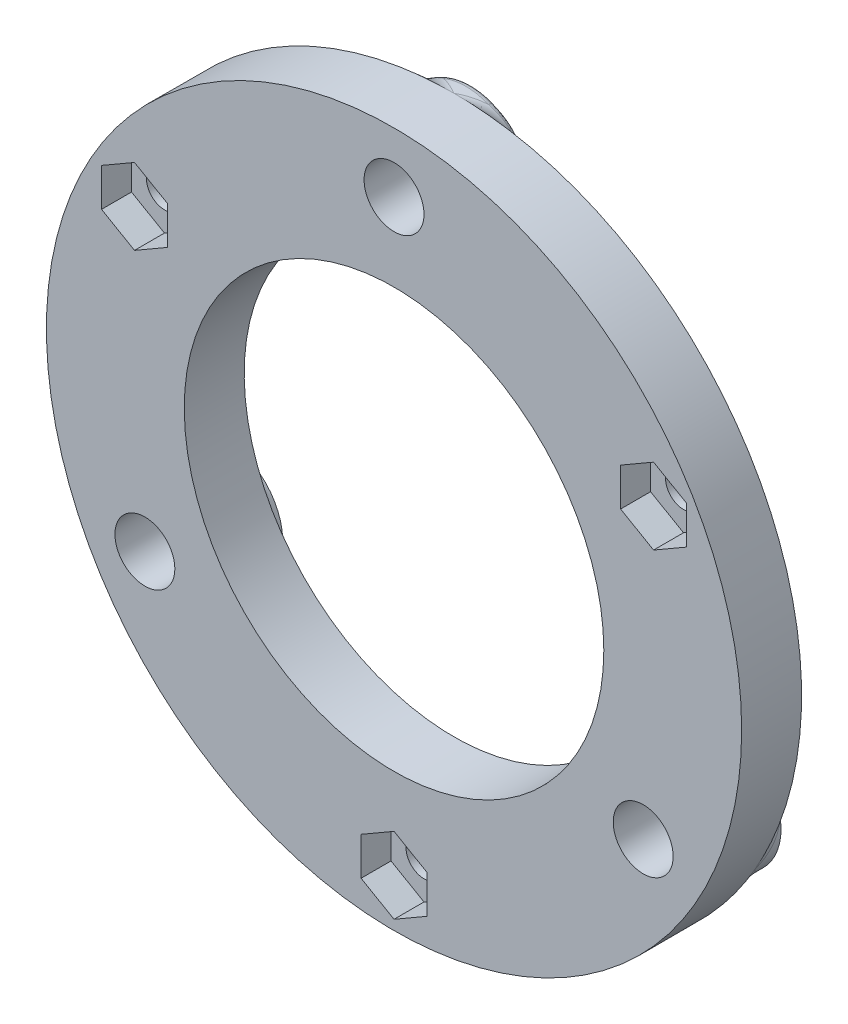
SolidWorks part; units mm, degrees
ref_plane "Front Plane" through (0, 0, 0) normal (0, 0, 1) x (1, 0, 0)
ref_plane "Top Plane" through (0, 0, 0) normal (0, 1, 0) x (1, 0, 0)
ref_plane "Right Plane" through (0, 0, 0) normal (1, 0, 0) x (0, 0, -1)
sketch "Sketch2" plane through (0, 0, 0) normal (0, 0, 1) x (1, 0, 0)
  line L0 (0, 24) -> (0, 0) construction
  line L1 (0, 0) -> (21.6506, 12.5) construction
  circle A0 centre (0, 0) radius 29
  circle A1 centre (0, 0) radius 17.5
  circle A2 centre (0, 0) radius 24 construction
  circle A3 centre (0, 24) radius 2.5
  circle A4 centre (0, 0) radius 25 construction
  circle A5 centre (20.7846, -12) radius 2.5
  circle A8 centre (21.6506, 12.5) radius 1.5
  circle A9 centre (0, -25) radius 1.5
  circle A11 centre (0, 0) radius 8 construction
  circle A14 centre (0, 24) radius 5 construction
  circle A15 centre (0, 0) radius 19 construction
  circle A16 centre (-20.7846, -12) radius 2.5
  circle A19 centre (-21.6506, 12.5) radius 1.5
  point P17 (0, 0)
  point P24 (0, 0)
  dimension "D1" = 58
  dimension "D2" = 48
  dimension "D4" = 5
  dimension "D7" = 3
  dimension "D3" = 16
  dimension "D10" = 10
  dimension "D5" = 4
  dimension "D9" = 1.5
  dimension "D11" = 60
  dimension "D6" = 3
  dimension "D8" = 3
extrude "Boss-Extrude1" add sketch "Sketch2" along normal blind 5
sketch "Sketch3" plane through (0, 0, 5) normal (0, 0, 1) x (1, 0, 0)
  line L0 (0, 24) -> (0, 0) construction
  line L13 (-0.5774, 24) -> (-0.2887, 23.5)
  line L14 (-0.2887, 23.5) -> (0.2887, 23.5)
  line L15 (0.2887, 23.5) -> (0.5774, 24)
  line L16 (0.5774, 24) -> (0.2887, 24.5)
  line L17 (0.2887, 24.5) -> (-0.2887, 24.5)
  line L18 (-0.2887, 24.5) -> (-0.5774, 24)
  line L20 (21.6506, 9.3246) -> (24.4006, 10.9123)
  line L21 (24.4006, 10.9123) -> (24.4006, 14.0877)
  line L22 (24.4006, 14.0877) -> (21.6506, 15.6754)
  line L23 (21.6506, 15.6754) -> (18.9006, 14.0877)
  line L24 (18.9006, 14.0877) -> (18.9006, 10.9123)
  line L25 (18.9006, 10.9123) -> (21.6506, 9.3246)
  circle A0 centre (0, 24) radius 0.5 construction
  circle A1 centre (21.6506, 12.5) radius 2.75 construction
  dimension "D1" = 1
  dimension "D2" = 5.5
extrude "Cut-Extrude1" cut sketch "Sketch3" against normal blind 2.5
pattern_circular "CirPattern1" count 3 over 360 about axis through (0, 0, 5) along (0, 0, -1) of "Cut-Extrude1" reverse direction yes
sketch "Sketch4" plane through (0, 0, 0) normal (0, 0, -1) x (-1, 0, 0)
  circle A0 centre (0, 24) radius 4
  circle A1 centre (0, 24) radius 5
  dimension "D1" = 8
extrude "Boss-Extrude2" add sketch "Sketch4" along normal blind 1.5
fillet "Fillet1" radius 1.5 1 edges at (-5, 24, 0)
fillet "Fillet2" radius 0.5 2 edges at (0, 29, -1.5) (0, 19, -1.5)
chamfer "Chamfer1" distance 0.25 angle 45 1 edges at (-4, 24, -1.5)
pattern_circular "CirPattern2" count 3 over 360 about axis through (0, 0, 5) along (0, 0, -1) of "Fillet1", "Boss-Extrude2", "Chamfer1" reverse direction yes
equation "\"Nr\"= \"Ns\" + 2 * \"Np\"'num teeth"
equation "\"module\"= 0.8"
equation "\"pressure_angle\"= 20deg"
equation "\"h_a\"= 1 * \"module\"'addendum"
equation "\"h_f\"= 1.25 * \"module\"'dedendum"
equation "\"clr_tip_root\"= \"h_f\" - \"h_a\"'clearance of gear tooth tip and root"
equation "\"dp_r\"= \"module\" * \"Nr\"'PCD"
equation "\"db_r\"= \"dp_r\" * cos ( \"pressure_angle\" )'base CD"
equation "\"fw_r\"= 11.5mm'face width"
equation "\"alpha_r\"= sqr ( \"dp_r\" ^ 2 - \"db_r\" ^ 2 ) / \"db_r\" * 180 / pi - \"pressure_angle\""
equation "\"beta_r\"= ( 360 / ( 4 * \"Nr\" ) + \"alpha_r\" ) * 2"
equation "\"bearing_ID\"= \"module\" * ( \"Ns\" + \"Np\" ) + 10"
equation "\"bearing_OD\"= 1.18 * \"bearing_ID\" + 8.57"
equation "\"bearing_height\"= 0.09 * \"bearing_ID\" + 4.62"
equation "\"clearance_planet\"=1.5"
equation "\"case_dist\"= \"sec_carrier_thickness\" + \"clearance_planet\" + \"standard_clearance_1_5mm\""
equation "\"Motor_case_OD_max\"= \"case_mounting_PCD\" + \"case_mounting_hole_allen_socket_dia\" + \"clearance_case_mount_holes_shell_thickness\" * 2"
equation "\"case_mounting_PCD\"= \"motor_case_OD_base\" + \"case_mounting_hole_shift\" * 2"
equation "\"bearing mount thickness\"= IIF((\"bearing_OD\" + \"output_mounting_hole_dia\" * 4) > (\"Nr\" * \"module\" + 2 * \"h_b\"), \"output_mounting_hole_dia\" * 2, ((\"Nr\" * \"module\" + 2 * \"h_b\" - (\"bearing_OD\" + \"output_mounting_hole_dia\" * 4)) / 2) + \"output_mounting_hole_dia\" * 2 + \"standard_clearance_1_5mm\")"
equation "\"case_mounting_hole_dia\"=3"
equation "\"output_mounting_PCD\"= \"bearing_OD\" + \"bearing mount thickness\""
equation "\"output_mounting_hole_dia\"= 4"
equation "\"clearance_case_mount_holes_shell_thickness\"= 1"
equation "\"motor_case_OD_base\"= \"motor_OD\" + \"clearance_motor_and_case\" * 2 + \"Motor_case_thickness\" * 2"
equation "\"sec_carrier_thickness\"= 5"
equation "\"sun_coupler_hub_thickness\"= 4"
equation "\"clearance_sun_coupler_sec_carrier\"= 1.5"
equation "\"clearance_motor_and_case\"= IIF(\"ring_OD\" < \"motor_OD\", 5, (\"ring_OD\" - \"motor_OD\")/2 + 5)"
equation "\"motor_OD\"= 88.6"
equation "\"Motor_case_thickness\"= 2.5"
equation "\"Motor_case_ID\"= \"motor_OD\" + \"clearance_motor_and_case\" * 2"
equation "\"case_mounting_hole_shift\"= \"case_mounting_hole_dia\" / 2 - 0.5"
equation "\"output_mounting_nut_wrench_size\"= 7"
equation "\"output_mounting_nut_thickness\"= 3.2"
equation "\"case_mounting_hole_allen_socket_dia\"= 5.5"
equation "\"output_mounting_nut_depth\"= 3"
equation "\"case_mounting_bolt_depth\"= 4.5"
equation "\"Ns\"= 20"
equation "\"Np\"= 40"
equation "\"ring_radial_thickness\"= 5"
equation "\"ring_OD\"= \"Nr\" * \"module\" + \"ring_radial_thickness\" * 2"
equation "\"ring_to_chamfer_clearance\"= 2"
equation "\"Motor_case_OD_base_to_chamfer\"=5"
equation "\"pattern_offset_from_motor_case_OD_base\"= 3"
equation "\"pattern_bulge_dia\"= 3"
equation "\"pattern_num_bulge\"= 18"
equation "\"pattern_depth\"= 2"
equation "\"motor_height\"= 43"
equation "\"case_mounting_wrench_size\"= 5.5"
equation "\"case_mounting_nut_clearance\"= 2"
equation "\"base_plate_thickness\"= 4"
equation "\"case_mounting_nut_thickness\"= 2.4"
equation "\"case_mounting_surface_height\"= 4"
equation "\"motor_mount_hole_PCD\"= 32"
equation "\"motor_mount_hole_dia\"= 4"
equation "\"motor_mount_hole_num\"= 4"
equation "\"central_hole_offset_from_motor_mount_PCD\"= 5"
equation "\"wire_slot_dist_from_center\"= 30"
equation "\"wire_slot_length\"= 10"
equation "\"wire_slot_radius\"= 4"
equation "\"driver_upper_holes_dist_from_center\"= 23"
equation "\"driver_lower_holes_dist_from_center\"= 15"
equation "\"driver_side_holes_dist_from_center\"= 20"
equation "\"driver_mount_holes_dia\"= 2.5"
equation "\"driver_mount_inserts_OD\"= 3.5"
equation "\"driver_mount_thickness\"= 1.5"
equation "\"driver_mount_height\"= 4"
equation "\"air_flow_hole_offset\"= 3"
equation "\"num_planet\"= 3"
equation "\"planet_pin_bolt_dia\"= 5"
equation "\"planet_pin_socket_head_dia\"= 8.5"
equation "\"carrier_PCD\"= ( \"Np\" + \"Ns\" ) * \"module\""
equation "\"D1@Sketch2\"=\"bearing_ID\""
equation "\"D2@Sketch2\"=\"carrier_PCD\""
equation "\"D4@Sketch2\"=\"planet_pin_bolt_dia\""
equation "\"D6@Sketch2\"=\"num_planet\""
equation "\"D8@Sketch2\"=\"num_planet\""
equation "\"D1@CirPattern1\"=\"num_planet\""
equation "\"planet_shaft_dia\"= 8"
equation "\"fw_p\"= \"fw_r\""
equation "\"planet_shaft_step_offset\"= 1"
equation "\"carrier_trapezoidal_support_sun_offset\"= 5"
equation "\"carrier_trapezoidal_support_hole_PCD_offset_bearing_ID\"= 4"
equation "\"carrier_trapezoidal_support_hole_dia\"= 3"
equation "\"carrier_trapezoidal_support_hole_socket_head_dia\"= 5.5"
equation "\"carrier_bearing_step_width\"= 1.5"
equation "\"standard_clearance_1_5mm\"=1.5"
equation "\"standard_fillet_1_5mm\"= 1.5"
equation "\"sun_shaft_bearing_OD\"= 16"
equation "\"sun_shaft_bearing_width\"= 4"
equation "\"standard_bearing_insertion_chamfer\"= 0.5"
equation "\"D7@Sketch2\"=\"carrier_trapezoidal_support_hole_dia\""
equation "\"D5@Sketch2\"=\"carrier_trapezoidal_support_hole_PCD_offset_bearing_ID\""
equation "\"D3@Sketch2\"=\"Ns\"*\"module\""
equation "\"carrier_trapezoidal_support_hole_wrench_size\"= 5.5"
equation "\"planet_pin_bolt_wrench_size\"= 8"
equation "\"D1@Boss-Extrude1\"=\"sec_carrier_thickness\""
equation "\"D1@Cut-Extrude1\"=\"sec_carrier_thickness\"/2"
equation "\"D1@Sketch4\"=\"planet_shaft_dia\""
equation "\"D2@Sketch4\"=\"planet_shaft_step_offset\""
equation "\"D1@Boss-Extrude2\"=\"clearance_planet\""
equation "\"D1@Fillet1\"=\"standard_fillet_1_5mm\""
equation "\"D1@Chamfer1\"=\"standard_bearing_insertion_chamfer\"/2"
equation "\"D1@Fillet2\"=\"standard_fillet_1_5mm\"/3"
equation "\"D1@CirPattern2\"=\"num_planet\""
equation "\"D10@Sketch2\"=\"planet_shaft_dia\"+\"planet_shaft_step_offset\"*2"
equation "\"D9@Sketch2\"=\"standard_clearance_1_5mm\""
equation "\"D1@Sketch3\"=\"planet_shaft_step_offset\""
equation "\"D11@Sketch2\"=180/\"num_planet\""
equation "\"D2@Sketch3\"=\"carrier_trapezoidal_support_hole_wrench_size\""
equation "\"pressure angle\"= 20deg"
equation "\"motor_output_hole_PCD\"= 23"
equation "\"motor_output_hole_dia\"= 4"
equation "\"motor_output_hole_num\"= 4"
equation "\"h_b\"= 1.25 * \"module\"'dedendum"
equation "\"dp_s\"= \"module\" * \"Ns\"'PCD"
equation "\"db_s\"= \"dp_s\" * cos ( \"pressure angle\" )'base CD"
equation "\"fw_s_calc\"= 13mm'face width"
equation "\"alpha_s\"= sqr ( \"dp_s\" ^ 2 - \"db_s\" ^ 2 ) / \"db_s\" * 180 / pi - \"pressure angle\""
equation "\"beta_s\"= ( 360 / ( 4 * \"Ns\" ) - \"alpha_s\" ) * 2"
equation "\"dp_p\"= \"module\" * \"Np\"'PCD"
equation "\"db_p\"= \"dp_p\" * cos ( \"pressure angle\" )'base CD"
equation "\"alpha_p\"= sqr ( \"dp_p\" ^ 2 - \"db_p\" ^ 2 ) / \"db_p\" * 180 / pi - \"pressure angle\""
equation "\"beta_p\"= ( 360 / ( 4 * \"Np\" ) - \"alpha_p\" ) * 2"
equation "\"planet_bearing_OD\"= 12"
equation "\"planet_bearing_width\"= 3"
equation "\"planet_bore\"= 10"
equation "\"sun_shaft_bearing_ID\"= 8"
equation "\"sun_hub_dia\"= \"motor_output_hole_PCD\" + \"motor_output_hole_dia\" + \"standard_clearance_1_5mm\" * 4"
equation "\"sun_central_bolt_dia\"= 5"
equation "\"sun_central_bolt_socket_head_dia\"= 8.5"
equation "\"fw_s_used\"= \"fw_p\" + \"clearance_planet\" + \"sec_carrier_thickness\" + \"standard_clearance_1_5mm\""
equation "\"motor_output_hole_CSK_OD\"= 9'8.96 is exact value"
equation "\"motor_output_hole_CSK_head_height\"= 2.5"
equation "\"bearing_retainer_thickness\"= 2"
equation "\"D4@Sketch4\"=\"carrier_trapezoidal_support_sun_offset\""
equation "\"D2@Sketch5\"=\"carrier_trapezoidal_support_hole_dia\""
equation "\"D1@Cut-Extrude2\"=\"carrier_trapezoidal_support_hole_dia\""
equation "\"D1@Sketch6\"=\"carrier_trapezoidal_support_hole_socket_head_dia\""
equation "\"D1@Cut-Extrude3\"=\"planet_pin_bolt_dia\""
equation "\"D1@Sketch7\"=\"planet_pin_socket_head_dia\""
equation "\"D1@Sketch9\"=\"sun_shaft_bearing_OD\""
equation "\"D1@Sketch10\"=\"standard_clearance_1_5mm\""
